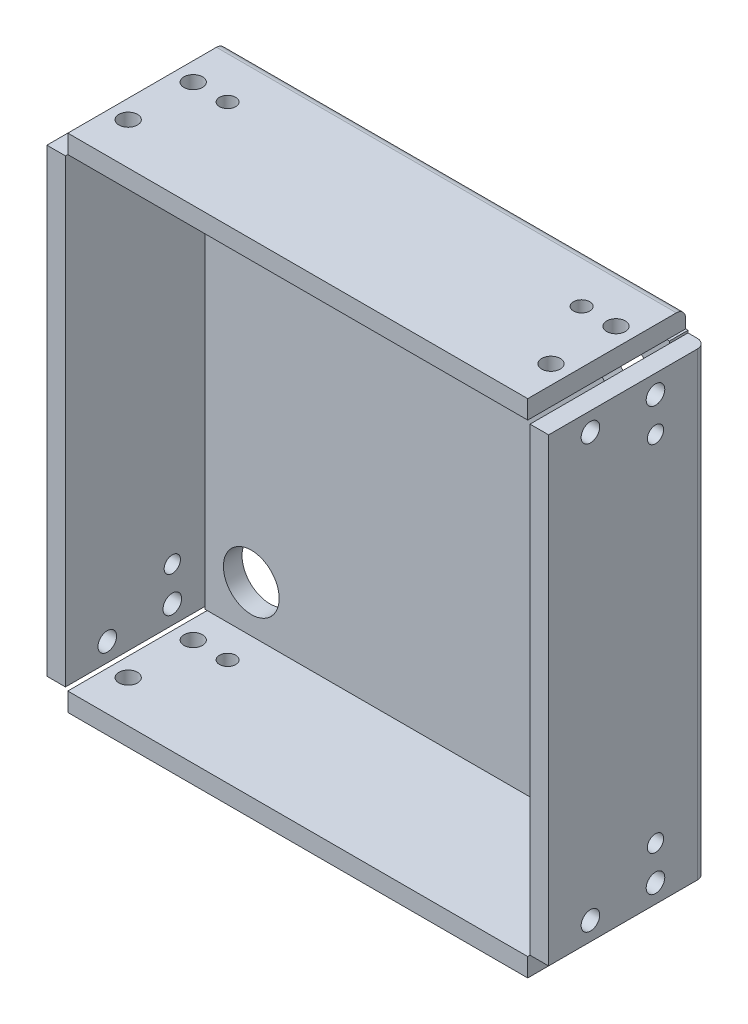
SolidWorks part; units mm, degrees
ref_plane "Front Plane" through (0, 0, 0) normal (0, 0, 1) x (1, 0, 0)
ref_plane "Top Plane" through (0, 0, 0) normal (0, 1, 0) x (1, 0, 0)
ref_plane "Right Plane" through (0, 0, 0) normal (1, 0, 0) x (0, 0, -1)
sketch "Sketch1" plane through (0, 0, 0) normal (0, 0, 1) x (1, 0, 0)
  line L2 (-97.668, 39.6138) -> (1.332, 39.6138)
  line L8 (1.332, -68.3862) -> (-97.668, -68.3862)
  line L11 (-102.168, -63.8862) -> (-102.168, 35.1138)
  line L12 (-98.168, 35.6138) -> (-98.168, -64.3862)
  line L13 (-98.168, -64.3862) -> (1.832, -64.3862)
  line L14 (1.332, 39.6138) -> (1.332, 35.6138)
  line L15 (-98.168, 35.6138) -> (1.832, 35.6138)
  line L16 (1.332, -68.3862) -> (1.332, -64.3862)
  line L17 (5.832, 35.1138) -> (5.832, -63.8862)
  line L18 (1.832, 35.6138) -> (1.832, -64.3862)
  line L19 (-97.668, 39.6138) -> (-97.668, 35.6138)
  line L20 (-102.168, 35.1138) -> (-98.168, 35.1138)
  line L21 (-102.168, -63.8862) -> (-98.168, -63.8862)
  line L22 (5.832, 35.1138) -> (1.832, 35.1138)
  line L23 (-97.668, -68.3862) -> (-97.668, -64.3862)
  line L24 (5.832, -63.8862) -> (1.832, -63.8862)
  circle A0 centre (-88.168, 25.6138) radius 6
  circle A1 centre (-8.168, 25.6138) radius 6
  circle A2 centre (-8.168, -54.3862) radius 6
  circle A3 centre (-88.168, -54.3862) radius 6
  dimension "D15" = 12
  dimension "D16" = 12
  dimension "D17" = 12
  dimension "D18" = 12
  dimension "D3" = 4
  dimension "D4" = 4
  dimension "D5" = 4
  dimension "D6" = 4
  dimension "D7" = 10
  dimension "D8" = 10
  dimension "D9" = 10
  dimension "D10" = 10
  dimension "D11" = 10
  dimension "D12" = 10
  dimension "D13" = 10
  dimension "D14" = 10
  dimension "D19" = 100
  dimension "D20" = 0.5
  dimension "D21" = 100
  dimension "D22" = 0.5
  dimension "D23" = 0.5
  dimension "D24" = 0.5
  dimension "D25" = 0.5
  dimension "D26" = 0.5
  dimension "D27" = 0.5
  dimension "D28" = 0.5
extrude "Boss-Extrude1" add sketch "Sketch1" along normal blind 4 contours L18 L15 L12 L13 A3 A2 A1 A0 region at (-48.168, -14.3862, 0)
extrude "Boss-Extrude3" add sketch "Sketch1<3>" along normal blind 34 contours L12 L11 | L15 L2 | L18 L17 | L13 L8 region at (-48.168, 37.6138, 0) region at (-100.168, -14.3862, 0) region at (3.832, -14.3862, 0) region at (-48.168, -66.3862, 0)
sketch "Sketch1<3>" plane through (0, 0, 0) normal (0, 0, 1) x (1, 0, 0) same geometry as "Sketch1"
fillet "Fillet3" radius 2 4 edges at (-48.168, 39.6138, 0) (-102.168, -14.3862, 0) (-48.168, -68.3862, 0) (5.832, -14.3862, 0)
sketch "Sketch2" plane through (-102.168, 0, 0) normal (-1, 0, 0) x (0, 0, 1)
  line L0 (34, -63.8862) -> (34, 35.1138) construction
  line L1 (34, 35.1138) -> (2, 35.1138) construction
  line L2 (34, -63.8862) -> (2, -63.8862) construction
  line L3 (2, 35.1138) -> (2, -63.8862) construction
  circle A0 centre (25, 31.1138) radius 2
  circle A1 centre (25, -59.8862) radius 2
  circle A2 centre (11, 31.1138) radius 2
  circle A3 centre (11, -59.8862) radius 2
  circle A4 centre (11, 23.7138) radius 1.75
  circle A5 centre (11, -52.4862) radius 1.75
  point P20 (0, 0)
  dimension "D1" = 4
  dimension "D2" = 4
  dimension "D7" = 4
  dimension "D8" = 4
  dimension "D11" = 3.5
  dimension "D12" = 3.5
  dimension "D3" = 9
  dimension "D4" = 9
  dimension "D5" = 4
  dimension "D6" = 4
  dimension "D9" = 9
  dimension "D10" = 9
  dimension "D13" = 23
  dimension "D14" = 23
  dimension "D15" = 76.2
  dimension "D16" = 11.4
  dimension "D17" = 4
  dimension "D18" = 4
extrude "Cut-Extrude1" cut sketch "Sketch2" against normal up to surface (4 mm away) up to face at (-98.168, -14.3862, 19)
sketch "Sketch3" plane through (0, -68.3862, 0) normal (0, -1, 0) x (1, 0, 0)
  line L0 (1.332, 34) -> (-97.668, 34) construction
  line L1 (1.332, 34) -> (1.332, 2) construction
  line L2 (-97.668, 34) -> (-97.668, 2) construction
  line L3 (-97.668, 2) -> (1.332, 2) construction
  line L4 (1.832, 34) -> (1.832, 4) construction
  circle A0 centre (-93.668, 25) radius 2
  circle A1 centre (-2.668, 25) radius 2
  circle A2 centre (-93.668, 11) radius 2
  circle A3 centre (-2.668, 11) radius 2
  circle A4 centre (-86.268, 11) radius 1.75
  circle A5 centre (-9.568, 11) radius 1.75
  dimension "D1" = 4
  dimension "D2" = 4
  dimension "D7" = 4
  dimension "D10" = 4
  dimension "D11" = 3.5
  dimension "D12" = 3.5
  dimension "D3" = 9
  dimension "D4" = 9
  dimension "D5" = 4
  dimension "D6" = 4
  dimension "D8" = 9
  dimension "D9" = 9
  dimension "D13" = 11.4
  dimension "D14" = 11.4
  dimension "D15" = 23
  dimension "D16" = 23
  dimension "D17" = 4
  dimension "D18" = 4
extrude "Cut-Extrude2" cut sketch "Sketch3" against normal up to surface (4 mm away) up to face at (-48.168, -64.3862, 19)
sketch "Sketch4" plane through (5.832, 0, 0) normal (1, 0, 0) x (0, 0, -1)
  line L0 (-34, 35.1138) -> (-34, -63.8862) construction
  line L1 (-34, -63.8862) -> (-2, -63.8862) construction
  line L2 (-34, 35.1138) -> (-2, 35.1138) construction
  line L3 (-2, -63.8862) -> (-2, 35.1138) construction
  circle A0 centre (-25, -59.8862) radius 2
  circle A1 centre (-25, 31.1138) radius 2
  circle A2 centre (-11, -59.8862) radius 2
  circle A3 centre (-11, 31.1138) radius 2
  circle A4 centre (-11, -52.4862) radius 1.75
  circle A5 centre (-11, 23.7138) radius 1.75
  dimension "D1" = 4
  dimension "D2" = 4
  dimension "D7" = 4
  dimension "D8" = 9
  dimension "D9" = 4
  dimension "D11" = 3.5
  dimension "D13" = 3.5
  dimension "D3" = 9
  dimension "D4" = 4
  dimension "D5" = 9
  dimension "D6" = 4
  dimension "D10" = 9
  dimension "D12" = 11.4
  dimension "D14" = 11.4
  dimension "D15" = 23
  dimension "D16" = 23
  dimension "D17" = 4
  dimension "D18" = 4
extrude "Cut-Extrude3" cut sketch "Sketch4" against normal up to surface (4 mm away) up to face at (1.832, -14.3862, 19)
sketch "Sketch5" plane through (0, 39.6138, 0) normal (0, 1, 0) x (1, 0, 0)
  line L0 (-97.668, -34) -> (-97.668, -2) construction
  line L1 (-97.668, -34) -> (1.332, -34) construction
  line L2 (1.332, -34) -> (1.332, -2) construction
  line L3 (1.332, -2) -> (-97.668, -2) construction
  circle A0 centre (-93.668, -25) radius 2
  circle A1 centre (-2.668, -25) radius 2
  circle A2 centre (-93.668, -11) radius 2
  circle A3 centre (-2.668, -11) radius 2
  circle A4 centre (-86.268, -11) radius 1.75
  circle A5 centre (-10.068, -11) radius 1.75
  dimension "D1" = 4
  dimension "D2" = 4
  dimension "D7" = 4
  dimension "D9" = 4
  dimension "D12" = 3.5
  dimension "D14" = 3.5
  dimension "D3" = 4
  dimension "D4" = 9
  dimension "D5" = 4
  dimension "D6" = 9
  dimension "D8" = 9
  dimension "D10" = 9
  dimension "D11" = 11.4
  dimension "D13" = 23
  dimension "D15" = 23
  dimension "D16" = 11.4
  dimension "D17" = 4
  dimension "D18" = 4
extrude "Cut-Extrude4" cut sketch "Sketch5" against normal up to surface (4 mm away) up to face at (-48.168, 35.6138, 19)
